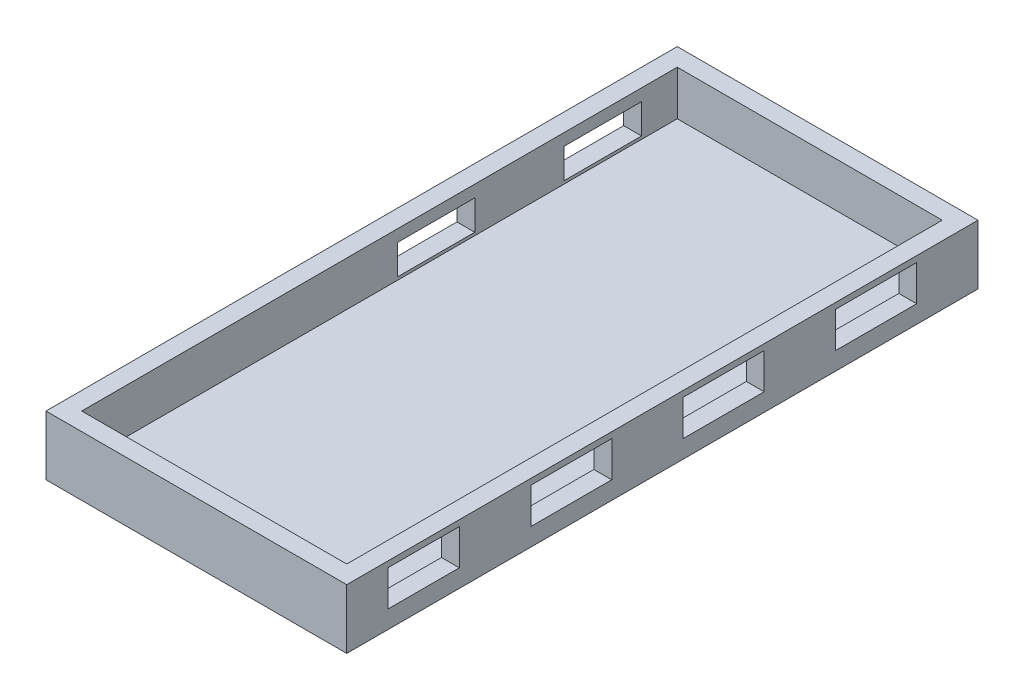
SolidWorks part; units mm, degrees
ref_plane "前视基准面" through (0, 0, 0) normal (0, 0, 1) x (1, 0, 0)
ref_plane "上视基准面" through (0, 0, 0) normal (0, 1, 0) x (1, 0, 0)
ref_plane "右视基准面" through (0, 0, 0) normal (1, 0, 0) x (0, 0, -1)
other "Configuration Table"
sketch "草图1" plane through (0, 0, 0) normal (0, 1, 0) x (1, 0, 0)
  line L1 (-21.0145, 20.2) -> (29.4855, 20.2)
  line L2 (-21.0145, 20.2) -> (-21.0145, -85.8)
  line L3 (-21.0145, -85.8) -> (29.4855, -85.8)
  line L4 (29.4855, 20.2) -> (29.4855, -85.8)
  dimension "D1" = 50.5
  dimension "D2" = 106
extrude "凸台-拉伸1" add sketch "草图1" along normal blind 10
sketch "草图4" plane through (0, 10, 0) normal (0, 1, 0) x (1, 0, 0)
  line L0 (29.4855, 20.2) -> (-21.0145, 20.2) construction
  line L1 (-18.0145, 17.2) -> (26.4855, 17.2)
  line L2 (-18.0145, 17.2) -> (-18.0145, -82.8)
  line L3 (-18.0145, -82.8) -> (26.4855, -82.8)
  line L4 (26.4855, 17.2) -> (26.4855, -82.8)
  line L5 (29.4855, -85.8) -> (29.4855, 20.2) construction
  dimension "D1" = 44.5
  dimension "D2" = 100
  dimension "D3" = 3
  dimension "D4" = 3
extrude "凸台-拉伸7" add sketch "草图4" against normal blind 7 contours L2 L1 L4 L3
extrude "切除-拉伸1" cut sketch "草图4<4>" against normal blind 7.5
sketch "草图4<4>" plane through (0, 10, 0) normal (0, 1, 0) x (1, 0, 0) same geometry as "草图4"
ref_plane "基准面2" through (-21.0145, 10, -20.2) normal (0, 0, 1) x (1, 0, 0)
sketch "草图6" plane through (-21.0145, 0, 0) normal (-1, 0, 0) x (0, 0, 1)
  line L0 (-20.2, -19.15) -> (-20.2, 39.15) construction
  line L1 (-11.2, 8) -> (1.8, 8)
  line L2 (-11.2, 8) -> (-11.2, 3)
  line L3 (-11.2, 3) -> (1.8, 3)
  line L4 (1.8, 8) -> (1.8, 3)
  line L5 (16.8, 8) -> (29.8, 8)
  line L6 (16.8, 8) -> (16.8, 3)
  line L7 (16.8, 3) -> (29.8, 3)
  line L8 (29.8, 8) -> (29.8, 3)
  line L13 (-20.2, 0) -> (85.8, 0) construction
  point P12 (0, 0)
  dimension "D1" = 5
  dimension "D2" = 13
  dimension "D3" = 5
  dimension "D4" = 13
  dimension "D5" = 9
  dimension "D6" = 15
  dimension "D7" = 3
  dimension "D8" = 3
extrude "切除-拉伸2" cut sketch "草图6" against normal blind 3
sketch "草图7" plane through (29.4855, 0, 0) normal (1, 0, 0) x (0, 0, -1)
  line L0 (20.2, 39.15) -> (20.2, -19.15) construction
  line L1 (-3.7, 9) -> (9.9, 9)
  line L2 (-3.7, 9) -> (-3.7, 3)
  line L3 (-3.7, 3) -> (9.9, 3)
  line L4 (9.9, 9) -> (9.9, 3)
  line L5 (-29.3, 9) -> (-15.7, 9)
  line L6 (-29.3, 9) -> (-29.3, 3)
  line L7 (-29.3, 3) -> (-15.7, 3)
  line L8 (-15.7, 9) -> (-15.7, 3)
  line L9 (-54.9, 9) -> (-41.3, 9)
  line L10 (-54.9, 9) -> (-54.9, 3)
  line L11 (-54.9, 3) -> (-41.3, 3)
  line L12 (-41.3, 9) -> (-41.3, 3)
  line L17 (-85.8, 0) -> (20.2, 0) construction
  line L18 (-78.9, 9) -> (-66.9, 9)
  line L19 (-78.9, 9) -> (-78.9, 3)
  line L20 (-78.9, 3) -> (-66.9, 3)
  line L21 (-66.9, 9) -> (-66.9, 3)
  point P20 (0, 0)
  point P21 (0, 0)
  dimension "D1" = 10.3
  dimension "D2" = 13.6
  dimension "D3" = 12
  dimension "D4" = 13.6
  dimension "D5" = 12
  dimension "D6" = 13.6
  dimension "D7" = 12
  dimension "D8" = 12
  dimension "D9" = 3
  dimension "D10" = 6
  dimension "D11" = 6
  dimension "D12" = 6
  dimension "D13" = 6
  dimension "D14" = 3
  dimension "D15" = 3
  dimension "D16" = 3
extrude "切除-拉伸3" cut sketch "草图7" against normal blind 3
